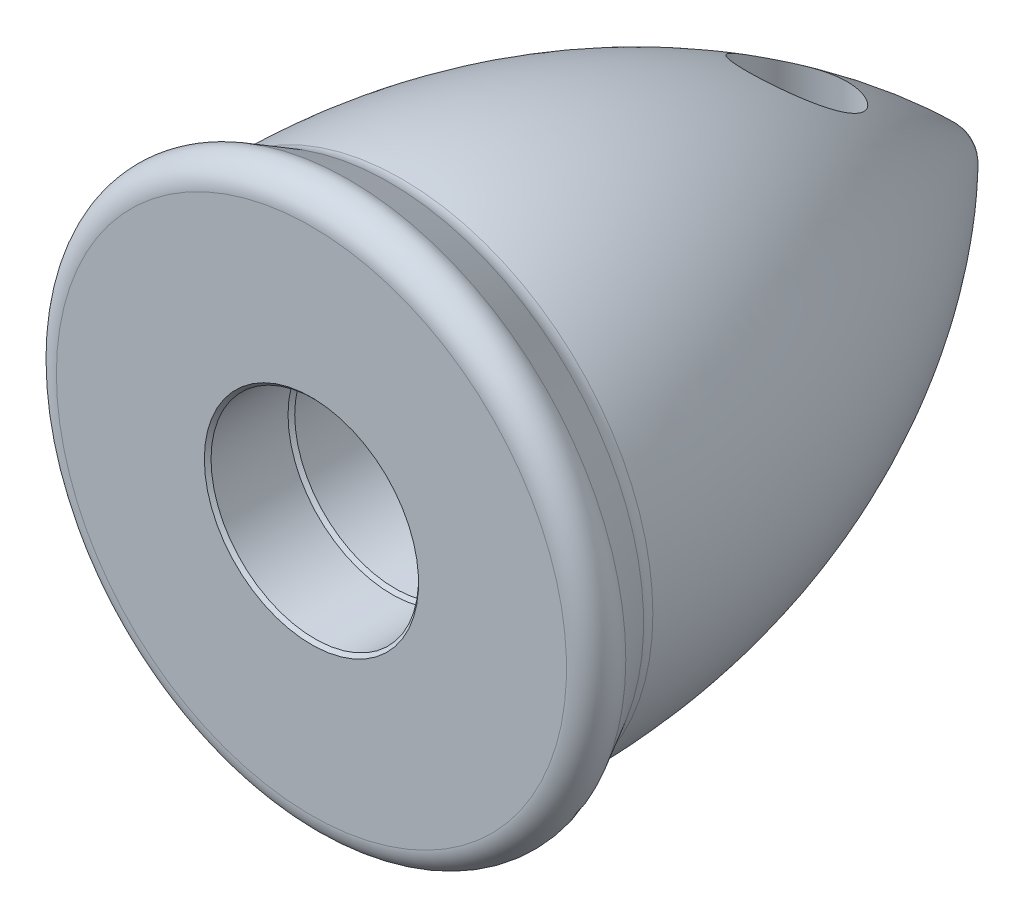
SolidWorks part; units mm, degrees
ref_plane "Ön Düzlem" through (0, 0, 0) normal (0, 0, 1) x (1, 0, 0)
ref_plane "Üst Düzlem" through (0, 0, 0) normal (0, 1, 0) x (1, 0, 0)
ref_plane "Sağ Düzlem" through (0, 0, 0) normal (1, 0, 0) x (0, 0, -1)
sketch "Çizim1" plane through (0, 0, 0) normal (0, 0, 1) x (1, 0, 0)
  circle A0 centre (0, 0) radius 7.5
  circle A1 centre (0, 0) radius 3
  dimension "D1" = 15
  dimension "D2" = 6
sketch "Çizim2" plane through (0, 0, 0) normal (0, 1, 0) x (1, 0, 0)
  line L0 (0, 0) -> (0, 2.0973)
  line L2 (0, 2.0973) -> (0, 19.5) construction
  line L3 (0, 14.0973) -> (7.8445, 14.0973) construction
  line L4 (2, 15.5973) -> (3.3668, 15.5973) construction
  line L5 (0, 19.0973) -> (0, 16.752)
  line L6 (3, 2.0973) -> (3, 11.3473)
  line L7 (-3, 2.0973) -> (-3, 19.5) construction
  line L8 (2, 15.5973) -> (0, 16.752)
  line L9 (2, 15.5973) -> (2, 12.5973)
  line L10 (0, 16.752) -> (0, 2.0973)
  line L11 (2, 12.3473) -> (2, 12.5973)
  line L12 (0, 2.0973) -> (0, -0.4027)
  line L13 (3.2, -0.4027) -> (7.6204, -0.4027)
  line L14 (7.598, 1.9223) -> (8.2748, 0.7137)
  line L15 (-3, 2.0973) -> (3, 2.0973)
  line L16 (3.1, 1.9973) -> (3.1, -0.3027)
  line L17 (3, 2.0973) -> (3.1, 1.9973)
  line L18 (3.1, -0.3027) -> (3.2, -0.4027)
  arc A0 (-0.7143, 18.7971) -> (0.7143, 18.7971) centre (0, 18.0973) cw
  arc A1 (2, 12.3473) -> (3, 11.3473) centre (3, 12.3473) ccw
  arc A2 (7.6204, -0.4027) -> (8.2748, 0.7137) centre (7.6204, 0.3473) ccw
  arc A3 (7.5024, 2.2947) -> (7.598, 1.9223) centre (8.2524, 2.2888) ccw
  spline S0 degree 3 poles (7.5024, 2.2947) (7.5297, 5.7478) (6.1834, 11.7595) (2.6765, 16.7942) (0.7143, 18.7971) knots 0.009809 0.009809 0.009809 0.009809 0.52502 0.949749 0.949749 0.949749 0.949749
  spline S1 degree 3 poles (-7.5, 2.0973) (-7.6042, 8.4739) (-5.1021, 14.3184) (-0.7143, 18.7971) knots 0 0 0 0 0.949749 0.949749 0.949749 0.949749
  point P6 (0, 2.0973)
  point P8 (0, 14.0973)
  point P18 (0, 19.0973)
  point P34 (3.1, 2.0973)
  point P35 (3.1, -0.4027)
  dimension "D1" = 1
  dimension "D6" = 0.75
  dimension "D8" = 0.75
  dimension "D2" = 12
  dimension "D4" = 17
  dimension "D7" = 30
  dimension "D3" = 2
  dimension "D5" = 2
revolve "Döndür1" add sketch "Çizim2" angle 360 about L10 region at (4.5235, 0, -7.4106)
sketch "Çizim3" plane through (0, 0, 0) normal (0, 1, 0) x (1, 0, 0)
  circle A0 centre (0, 14.0973) radius 1.5
extrude "Kes-Ekstrüzyon1" cut sketch "Çizim3" against normal blind 10 and the other way blind 10
